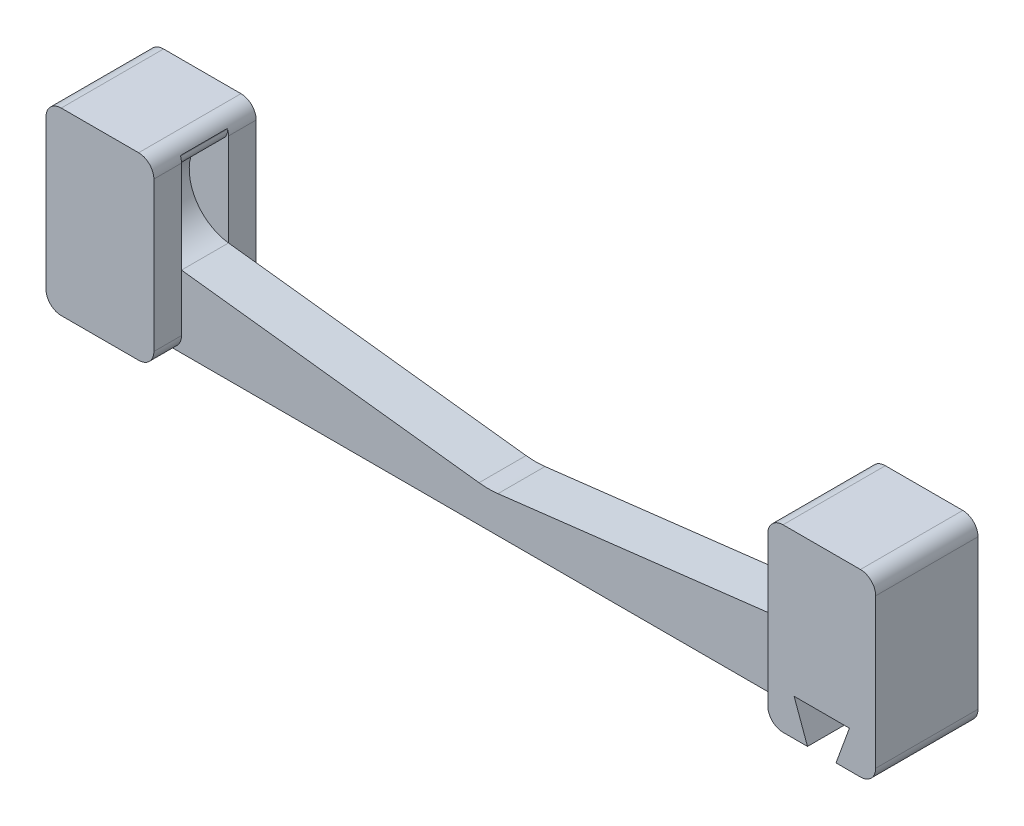
SolidWorks part; units mm, degrees
ref_plane "Front Plane" through (0, 0, 0) normal (0, 0, 1) x (1, 0, 0)
ref_plane "Top Plane" through (0, 0, 0) normal (0, 1, 0) x (1, 0, 0)
ref_plane "Right Plane" through (0, 0, 0) normal (1, 0, 0) x (0, 0, -1)
sketch "Sketch1" plane through (0, 0, 0) normal (0, 1, 0) x (1, 0, 0)
  line L1 (-19.05, -1.0795) -> (19.05, -1.0795)
  line L2 (-19.05, -1.0795) -> (-19.05, 1.0795)
  line L3 (-19.05, 1.0795) -> (19.05, 1.0795)
  line L4 (19.05, -1.0795) -> (19.05, 1.0795)
  line L5 (-19.05, -1.0795) -> (19.05, 1.0795) construction
  line L6 (-19.05, 1.0795) -> (19.05, -1.0795) construction
  point P0 (0, 0)
  dimension "D1" = 2.159
  dimension "D2" = 38.1
extrude "Boss-Extrude1" add sketch "Sketch1" along normal blind 8.255
sketch "Sketch2" plane through (0, 0, 1.0795) normal (0, 0, 1) x (1, 0, 0)
  line L0 (0, 8.255) -> (0, 0) construction
  line L1 (-19.05, 8.255) -> (19.05, 8.255) construction
  line L2 (0, 5.334) -> (14.097, 5.334) construction
  line L3 (0.4351, 8.9912) -> (14.097, 7.366) construction
  line L4 (14.097, 5.334) -> (14.097, 7.366) construction
  line L5 (15.9016, 5.334) -> (14.097, 5.334) construction
  line L6 (0.4351, 1.6768) -> (14.097, 3.302)
  line L7 (-0.4351, 1.6768) -> (-14.097, 3.302)
  line L8 (-0.4351, 8.9912) -> (-14.097, 7.366) construction
  line L9 (14.097, 7.366) -> (14.8394, 13.6065)
  line L11 (0.4351, 13.6646) -> (14.8394, 13.6065)
  line L12 (-14.097, 7.366) -> (-14.6923, 12.3704)
  line L13 (-14.6923, 12.3704) -> (-0.4351, 13.6646)
  line L14 (-0.4351, 13.6646) -> (0.4351, 13.6646)
  circle A0 centre (0, 5.334) radius 3.683 construction
  arc A1 (14.097, 7.366) -> (14.097, 3.302) centre (13.8553, 5.334) cw
  arc A2 (-14.097, 7.366) -> (-14.097, 3.302) centre (-13.8553, 5.334) ccw
  arc A3 (-0.4351, 1.6768) -> (0.4351, 1.6768) centre (0, 5.334) ccw
  line M14 (19.05, 8.255) -> (-19.05, 8.255)
  dimension "D1" = 7.366
  dimension "D2" = 14.097
  dimension "D3" = 2.032
  dimension "D4" = 2.921
extrude "Cut-Extrude1" cut sketch "Sketch2" against normal blind 12.7 contours L7 A3 L6 A1 L9 L12 A2 M14 region at (0, 5.3403, 1.0795)
sketch "Sketch3" plane through (0, 0, 1.0795) normal (0, 0, 1) x (1, 0, 0)
  line L0 (-14.2028, 8.255) -> (-13.5874, 8.255) construction
  line L1 (-14.097, 7.366) -> (-14.097, 8.255) construction
  line L3 (-14.097, 8.255) -> (-19.05, 8.255)
  line L4 (-14.097, 8.255) -> (-14.097, 0)
  line L5 (-14.097, 0) -> (-19.05, 0)
  line L6 (-19.05, 8.255) -> (-19.05, 0)
extrude "Boss-Extrude2" add sketch "Sketch3" along normal blind 1.27
fillet "Fillet5" radius 0.4826 4 edges at (14.2028, 8.255, 0) (14.097, 7.366, 0) (-14.097, 7.366, 0) (-14.2028, 8.255, 0)
mirror "Mirror1" about plane through (0, 0, 0) normal (1, 0, 0) of "Boss-Extrude2"
ref_plane "Plane1" through (0, 0, 0) normal (0, 0, 1) x (1, 0, 0)
mirror "Mirror2" about plane through (0, 0, 0) normal (0, 0, 1) of "Mirror1", "Boss-Extrude2"
sketch "Sketch4" plane through (0, 0, 2.3495) normal (0, 0, 1) x (1, 0, 0)
  line L0 (16.5735, 0) -> (16.5735, 1.6891) construction
  line L1 (19.05, 0) -> (14.097, 0) construction
  line L2 (15.3035, 1.6891) -> (17.8435, 1.6891)
  line L3 (17.8435, 1.6891) -> (17.2287, 0)
  line L4 (15.3035, 1.6891) -> (15.9183, 0)
  line L5 (17.2287, 0) -> (15.9183, 0)
  point P6 (16.5735, 1.6891)
  dimension "D1" = 2.54
  dimension "D2" = 70
  dimension "D3" = 70
  dimension "D4" = 1.6891
extrude "Cut-Extrude2" cut sketch "Sketch4" against normal through all
fillet "Fillet6" radius 0.6985 12 edges at (-19.05, 8.255, 0) (-14.097, 8.255, 1.7145) (-14.097, 8.255, -1.7145) (14.097, 8.255, -1.7145) (14.097, 8.255, 1.7145) (19.05, 8.255, 0) (-19.05, 0, 0) (19.05, 0, 0) (14.097, 0, -1.7145) (14.097, 0, 1.7145) (-14.097, 0, -1.7145) (-14.097, 0, 1.7145)
